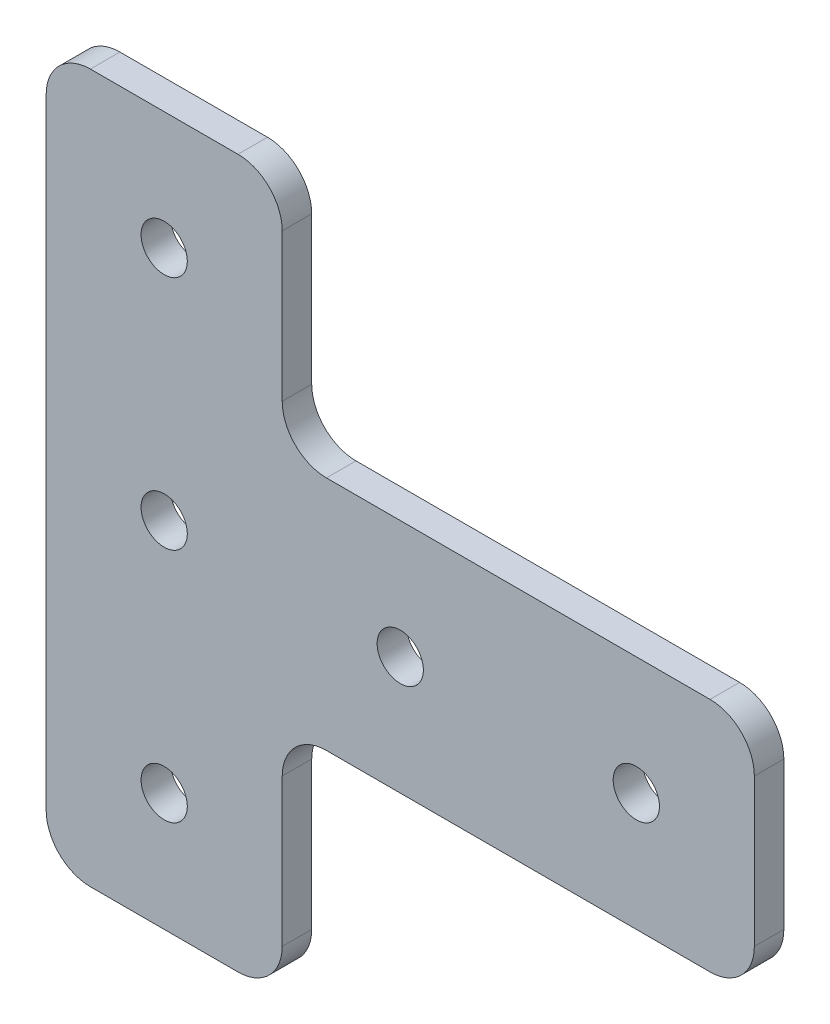
SolidWorks part; units mm, degrees
material "6061-T6 (SS)"
ref_plane "Front Plane" through (0, 0, 0) normal (0, 0, 1) x (1, 0, 0)
ref_plane "Top Plane" through (0, 0, 0) normal (0, 1, 0) x (1, 0, 0)
ref_plane "Right Plane" through (0, 0, 0) normal (1, 0, 0) x (0, 0, -1)
sketch "Sketch1" plane through (0, 0, 0) normal (0, 0, 1) x (1, 0, 0)
  line L0 (0, 0) -> (0, 76.2)
  line L1 (0, 76.2) -> (25.4, 76.2)
  line L2 (25.4, 76.2) -> (25.4, 50.8)
  line L3 (25.4, 50.8) -> (76.2, 50.8)
  line L4 (76.2, 50.8) -> (76.2, 25.4)
  line L5 (76.2, 25.4) -> (25.4, 25.4)
  line L6 (25.4, 25.4) -> (25.4, 0)
  line L7 (25.4, 0) -> (0, 0)
  line L8 (76.2, 38.1) -> (0, 38.1) construction
  circle A0 centre (12.7, 63.5) radius 2.4892
  circle A1 centre (12.7, 38.1) radius 2.4892
  circle A2 centre (12.7, 12.7) radius 2.4892
  circle A3 centre (38.1, 38.1) radius 2.4892
  circle A5 centre (63.5, 38.1) radius 2.4892
  point P13 (12.7, 76.2)
  point P20 (38.088, 39.4011)
  point P23 (0, 38.1)
  dimension "D5" = 4.9784
  dimension "D7" = 3
  dimension "D1" = 25.4
  dimension "D2" = 25.4
  dimension "D3" = 25.4
  dimension "D4" = 76.2
  dimension "D6" = 12.7
  dimension "D8" = 25.4
  dimension "D9" = 25.4
  dimension "D10" = 25.4
extrude "Boss-Extrude1" add sketch "Sketch1" along normal mid plane 3.175 contours L0 L1 L2 L3 L4 L5 L6 L7 | A0 | A2 | A1 | A3 | A5
fillet "Fillet1" radius 4.7625 8 edges at (0, 0, 0) (0, 76.2, 0) (76.2, 50.8, 0) (76.2, 25.4, 0) (25.4, 25.4, 0) (25.4, 0, 0) (25.4, 50.8, 0) (25.4, 76.2, 0)
